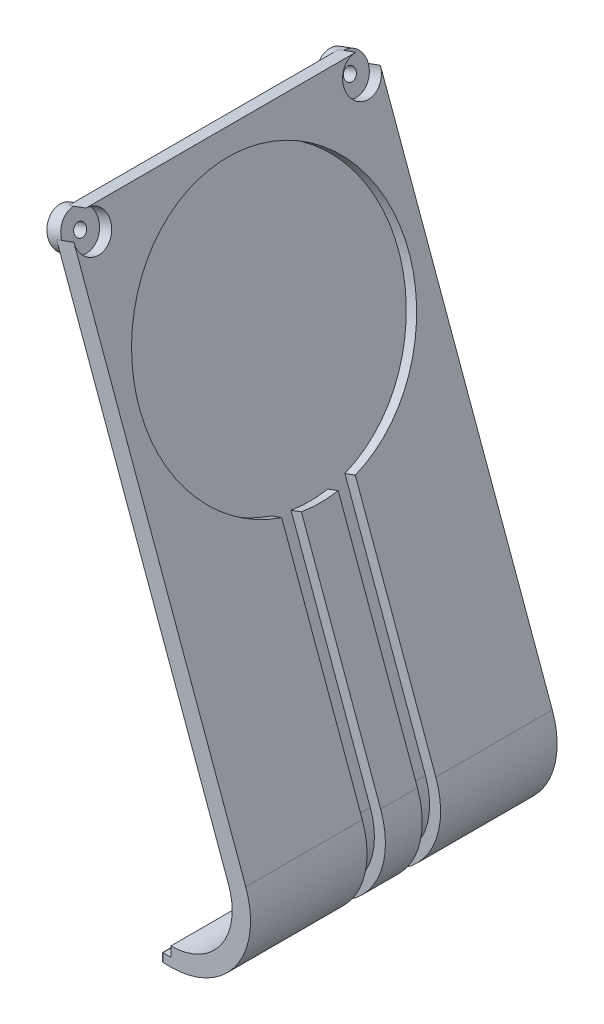
SolidWorks part; units mm, degrees
material "PLA"
ref_plane "前视基准面" through (0, 0, 0) normal (0, 0, 1) x (1, 0, 0)
ref_plane "上视基准面" through (0, 0, 0) normal (0, 1, 0) x (1, 0, 0)
ref_plane "右视基准面" through (0, 0, 0) normal (1, 0, 0) x (0, 0, -1)
other "Configuration Table"
sketch "草图2" plane through (0, 0, 0) normal (0, 0, 1) x (1, 0, 0)
  line L0 (40.5059, 20.4699) -> (9.8204, 104.7777) construction
  line L5 (40.5059, 20.4699) -> (11.4415, 100.3236)
  line L10 (31.109, 7.0497) -> (31.109, 6.0497) construction
  line L11 (10.418, 106.0594) -> (12.7673, 106.9145) construction
  arc A0 (31.109, 7.0497) -> (40.5059, 20.4699) centre (31.109, 17.0497) ccw
  arc A1 (31.109, 7.0497) -> (40.5059, 20.4699) centre (31.109, 17.0497) ccw construction
  point P0 (0, 0)
  dimension "D2" = 10
  dimension "D1" = 5.74
extrude "整体拉伸-薄壁1" add sketch "草图2" along normal mid plane 50 thin thin type one direction wall 3
sketch "草图4" plane through (45.1656, 16.4389, 0) normal (0.9397, 0.342, 0) x (0, 0, -1)
  line L0 (-25, 90.3601) -> (25, 90.3601) construction
  circle A0 centre (0, 64.9601) radius 22
  dimension "D1" = 44
  dimension "D2" = 25.4
extrude "中间圆切除-拉伸1" cut sketch "草图4" against normal blind 1.8
sketch "草图3" plane through (0, 0, 0) normal (0, 0, 1) x (1, 0, 0)
  line L0 (43.325, 21.4959) -> (14.2606, 101.3496) construction
  line L1 (43.325, 21.4959) -> (14.2606, 101.3496) construction
  line L2 (31.109, 4.0497) -> (31.109, 7.0497) construction
  line L5 (41.6335, 20.8803) -> (28.7809, 56.1926)
  line L6 (41.6335, 20.8803) -> (12.5692, 100.734) construction
  line L7 (31.109, 5.8497) -> (31.109, 5.8497) construction
  line L9 (28.7809, 56.1926) -> (30.4724, 56.8082) construction
  line L16 (28.7809, 56.1926) -> (27.7549, 59.0116)
  line L17 (29.3117, 5.9492) -> (20.226, 9.9391) construction
  arc A0 (31.109, 7.0497) -> (40.5059, 20.4699) centre (31.109, 17.0497) ccw construction
  arc A1 (20.226, 9.9391) -> (43.325, 21.4959) centre (31.109, 17.0497) ccw construction
  arc A2 (31.109, 5.8497) -> (41.6335, 20.8803) centre (31.109, 17.0497) ccw
  dimension "D2" = 3
  dimension "D1" = 1.8
extrude "线槽切除-拉伸-薄壁1" cut sketch "草图3" against normal blind 3 from offset 6 thin thin type one direction wall 1.8
mirror "镜向1" about plane through (0, 0, 0) normal (0, 0, 1) of "线槽切除-拉伸-薄壁1"
sketch "草图7" plane through (42.3465, 15.4129, 0) normal (-0.9397, -0.342, 0) x (0, 0, 1)
  line L0 (25, 90.3601) -> (-25, 90.3601) construction
  line L1 (-25, 5.3816) -> (-25, 90.3601) construction
  line L3 (0, 90.3601) -> (0, 71.6076) construction
  circle A0 centre (-22, 87.3601) radius 1
  circle A1 centre (-22, 87.3601) radius 3
  circle A2 centre (22, 87.3601) radius 3
  circle A3 centre (22, 87.3601) radius 1
  dimension "D1" = 2
extrude "螺丝柱凸台-拉伸2" add sketch "草图7" along normal blind 1.5
sketch "草图8" plane through (42.3465, 15.4129, 0) normal (-0.9397, -0.342, 0) x (0, 0, 1)
  line L0 (0, 90.3601) -> (0, 70.5485) construction
  line L1 (-26, 91.3601) -> (-22, 91.3601)
  line L2 (-26, 91.3601) -> (-26, 87.3601)
  line L3 (-26, 87.3601) -> (-25, 87.3601)
  line L4 (-22, 91.3601) -> (-22, 90.3601)
  line L5 (22, 90.3601) -> (-22, 90.3601) construction
  line L6 (22, 91.3601) -> (22, 90.3601)
  line L7 (26, 87.3601) -> (25, 87.3601)
  line L8 (26, 91.3601) -> (26, 87.3601)
  line L9 (26, 91.3601) -> (22, 91.3601)
  line L10 (-25, 5.3816) -> (-25, 87.3601) construction
  arc A0 (-25, 87.3601) -> (-22, 90.3601) centre (-22, 87.3601) ccw
  arc A2 (25, 87.3601) -> (22, 90.3601) centre (22, 87.3601) cw
  dimension "D2" = 4
  dimension "D3" = 4
  dimension "D4" = 1
  dimension "D5" = 1
extrude "螺丝柱切除-拉伸1" cut sketch "草图8" along normal blind 2.1 from surface starting at face at (30.929, 55.5537, 0)
sketch "草图9" plane through (42.3465, 15.4129, 0) normal (-0.9397, -0.342, 0) x (0, 0, 1)
  line L0 (-22, 90.3601) -> (-25, 90.3601) construction
  line L1 (-22, 90.3601) -> (-25, 90.3601)
  line L2 (-25, 87.3601) -> (-25, 90.3601) construction
  line L3 (-25, 87.3601) -> (-25, 90.3601)
  line L4 (0, 90.3601) -> (0, 58.5215) construction
  line L5 (22, 90.3601) -> (-22, 90.3601) construction
  line L6 (25, 87.3601) -> (25, 90.3601)
  line L7 (22, 90.3601) -> (25, 90.3601)
  circle A0 centre (-22, 87.3601) radius 3 construction
  arc A1 (-22, 90.3601) -> (-25, 87.3601) centre (-22, 87.3601) ccw
  arc A2 (22, 90.3601) -> (25, 87.3601) centre (22, 87.3601) cw
extrude "螺丝使圆切除-拉伸2" cut sketch "草图9" against normal up to next
sketch "草图10" plane through (42.3465, 15.4129, 0) normal (-0.9397, -0.342, 0) x (0, 0, 1)
  circle A0 centre (22, 87.3601) radius 1 construction
  circle A1 centre (22, 87.3601) radius 1
  circle A2 centre (-22, 87.3601) radius 1 construction
  circle A3 centre (-22, 87.3601) radius 1
extrude "螺丝孔切除-拉伸3" cut sketch "草图10" against normal mid plane 5
sketch "草图11" plane through (31.109, 0, 0) normal (-1, 0, 0) x (0, 0, 1)
  line L0 (-25, 4.0497) -> (-25, 7.0497) construction
  line L1 (-25, 5.4497) -> (-6.1, 5.4497)
  line L2 (-25, 5.4497) -> (-25, 4.0497)
  line L3 (-25, 4.0497) -> (-6.1, 4.0497)
  line L4 (-6.1, 5.4497) -> (-6.1, 4.0497)
  line L5 (25, 4.0497) -> (6, 4.0497) construction
  line L6 (6.1, 5.4497) -> (25, 5.4497)
  line L7 (6.1, 5.4497) -> (6.1, 4.0497)
  line L8 (6.1, 4.0497) -> (25, 4.0497)
  line L9 (25, 5.4497) -> (25, 4.0497)
  line L11 (-6, 4.0497) -> (-6, 5.8497) construction
  line L13 (6, 4.0497) -> (6, 5.8497) construction
  line L14 (25, 7.0497) -> (-25, 7.0497) construction
  dimension "D1" = 1.6
  dimension "D2" = 0.1
  dimension "D3" = 0.1
  dimension "D4" = 1.6
extrude "底部卡扣凸台-拉伸3" add sketch "草图11" along normal blind 1.5
fillet "底部卡扣圆角1" radius 0.25 8 edges at (29.609, 5.4497, 15.55) (29.609, 4.7497, 25) (29.609, 4.0497, 15.55) (29.609, 4.7497, 6.1) (29.609, 5.4497, -15.55) (29.609, 4.7497, -6.1) (29.609, 4.0497, -15.55) (29.609, 4.7497, -25)
